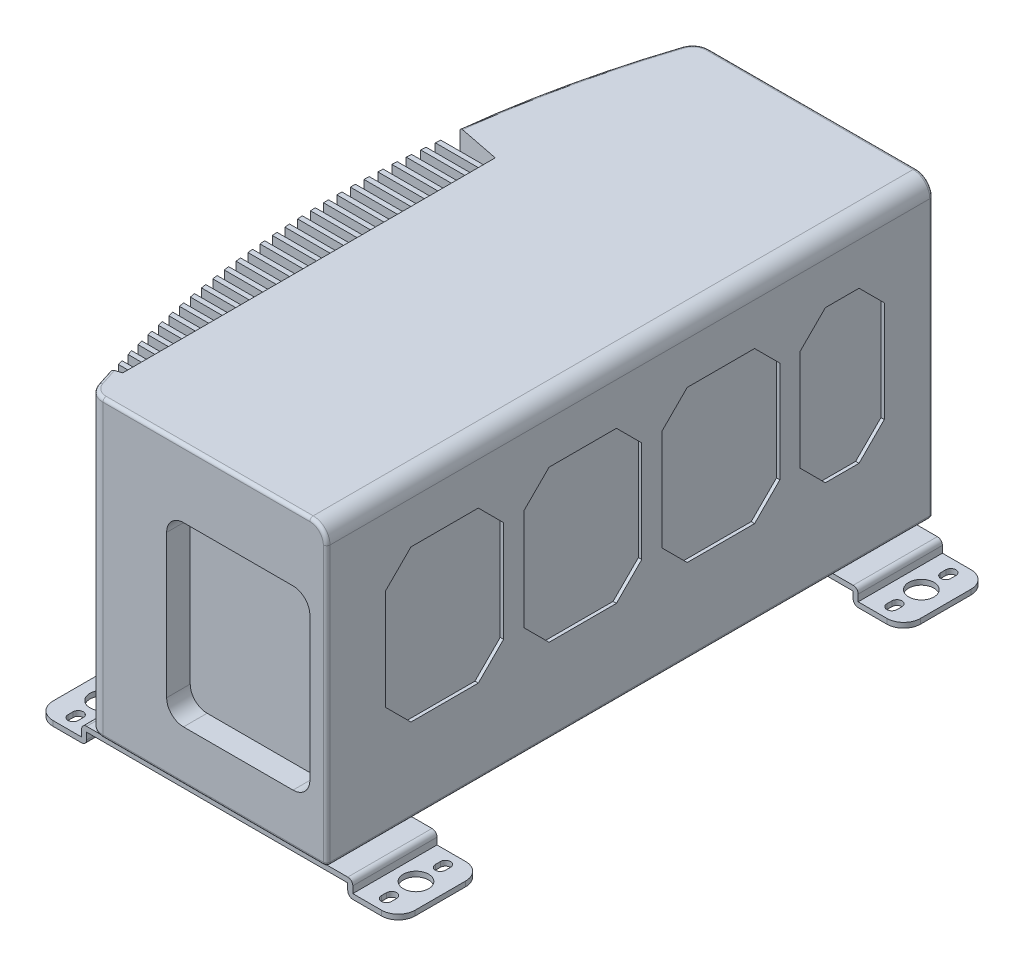
SolidWorks part; units mm, degrees
ref_plane "정면" through (0, 0, 0) normal (0, 0, 1) x (1, 0, 0)
ref_plane "윗면" through (0, 0, 0) normal (0, 1, 0) x (1, 0, 0)
ref_plane "우측면" through (0, 0, 0) normal (1, 0, 0) x (0, 0, -1)
sketch "스케치1" plane through (0, 0, 0) normal (0, 1, 0) x (1, 0, 0)
  line L0 (70, 0) -> (-100, 0) construction
  line L1 (-70, 180) -> (70, 180)
  line L2 (-70, 0) -> (-70, -180)
  line L3 (-70, -180) -> (70, -180)
  line L4 (70, 180) -> (70, -180)
  line L5 (-70, 180) -> (70, -180) construction
  line L6 (-70, -180) -> (70, 180) construction
  arc A0 (-70, 180) -> (-70, -180) centre (455, 0) ccw
  point P0 (0, 0)
  dimension "D1" = 360
  dimension "D2" = 140
  dimension "D3" = 170
extrude "보스-돌출1" add sketch "스케치1" along normal blind 175 contours L1 A0 L3 L4 region at (-10.3031, 0, 0)
sketch "스케치2" plane through (0, 175, 0) normal (0, 1, 0) x (1, 0, 0)
  line L0 (70, 0) -> (-70, 0) construction
  line L1 (-70, 60) -> (-70, -160) construction
  line L2 (70, 180) -> (70, -180) construction
  line L3 (-70, -180) -> (70, -180) construction
  line L4 (-130.1744, 60) -> (-70, 60)
  line L5 (-70, 60) -> (-70, 55)
  line L6 (-70, 55) -> (-130.1744, 55)
  line L7 (-130.1744, 55) -> (-130.1744, 52)
  line L8 (-130.1744, 52) -> (-70, 52)
  line L9 (-70, 52) -> (-70, 47)
  line L10 (-70, 47) -> (-130.1744, 47)
  line L11 (-130.1744, 47) -> (-130.1744, 44)
  line L12 (-130.1744, 44) -> (-70, 44)
  line L13 (-70, 44) -> (-70, 39)
  line L14 (-70, 39) -> (-130.1744, 39)
  line L15 (-130.1744, 39) -> (-130.1744, 36)
  line L16 (-130.1744, 36) -> (-70, 36)
  line L17 (-70, 36) -> (-70, 31)
  line L18 (-70, 31) -> (-130.1744, 31)
  line L19 (-130.1744, 31) -> (-130.1744, 28)
  line L20 (-130.1744, 28) -> (-70, 28)
  line L21 (-70, 28) -> (-70, 23)
  line L22 (-70, 23) -> (-130.1744, 23)
  line L23 (-130.1744, 23) -> (-130.1744, 20)
  line L24 (-130.1744, 20) -> (-70, 20)
  line L25 (-70, 20) -> (-70, 15)
  line L26 (-70, 15) -> (-130.1744, 15)
  line L27 (-130.1744, 15) -> (-130.1744, 12)
  line L28 (-130.1744, 12) -> (-70, 12)
  line L29 (-70, 12) -> (-70, 7)
  line L30 (-70, 7) -> (-130.1744, 7)
  line L31 (-130.1744, 7) -> (-130.1744, 4)
  line L32 (-130.1744, 4) -> (-70, 4)
  line L33 (-70, 4) -> (-70, -1)
  line L34 (-70, -1) -> (-130.1744, -1)
  line L35 (-130.1744, -1) -> (-130.1744, -4)
  line L36 (-130.1744, -4) -> (-70, -4)
  line L37 (-70, -4) -> (-70, -9)
  line L38 (-70, -9) -> (-130.1744, -9)
  line L39 (-130.1744, -9) -> (-130.1744, -12)
  line L40 (-130.1744, -12) -> (-70, -12)
  line L41 (-70, -12) -> (-70, -17)
  line L42 (-70, -17) -> (-130.1744, -17)
  line L43 (-130.1744, -17) -> (-130.1744, -20)
  line L44 (-130.1744, -20) -> (-70, -20)
  line L45 (-70, -20) -> (-70, -25)
  line L46 (-70, -25) -> (-130.1744, -25)
  line L47 (-130.1744, -25) -> (-130.1744, -28)
  line L48 (-130.1744, -28) -> (-70, -28)
  line L49 (-70, -28) -> (-70, -33)
  line L50 (-70, -33) -> (-130.1744, -33)
  line L51 (-130.1744, -33) -> (-130.1744, -36)
  line L52 (-130.1744, -36) -> (-70, -36)
  line L53 (-70, -36) -> (-70, -41)
  line L54 (-70, -41) -> (-130.1744, -41)
  line L55 (-130.1744, -41) -> (-130.1744, -44)
  line L56 (-130.1744, -44) -> (-70, -44)
  line L57 (-70, -44) -> (-70, -49)
  line L58 (-70, -49) -> (-130.1744, -49)
  line L59 (-130.1744, -49) -> (-130.1744, -52)
  line L60 (-130.1744, -52) -> (-70, -52)
  line L61 (-70, -52) -> (-70, -57)
  line L62 (-70, -57) -> (-130.1744, -57)
  line L63 (-130.1744, -57) -> (-130.1744, -60)
  line L64 (-130.1744, -60) -> (-70, -60)
  line L65 (-70, -60) -> (-70, -65)
  line L66 (-70, -65) -> (-130.1744, -65)
  line L67 (-130.1744, -65) -> (-130.1744, -68)
  line L68 (-130.1744, -68) -> (-70, -68)
  line L69 (-70, -68) -> (-70, -73)
  line L70 (-70, -73) -> (-130.1744, -73)
  line L71 (-130.1744, -73) -> (-130.1744, -76)
  line L72 (-130.1744, -76) -> (-70, -76)
  line L73 (-70, -76) -> (-70, -81)
  line L74 (-70, -81) -> (-130.1744, -81)
  line L75 (-130.1744, -81) -> (-130.1744, -84)
  line L76 (-130.1744, -84) -> (-70, -84)
  line L77 (-70, -84) -> (-70, -89)
  line L78 (-70, -89) -> (-130.1744, -89)
  line L79 (-130.1744, -89) -> (-130.1744, -92)
  line L80 (-130.1744, -92) -> (-70, -92)
  line L81 (-70, -92) -> (-70, -97)
  line L82 (-70, -97) -> (-130.1744, -97)
  line L83 (-130.1744, -97) -> (-130.1744, -100)
  line L84 (-130.1744, -100) -> (-70, -100)
  line L85 (-70, -100) -> (-70, -105)
  line L86 (-70, -105) -> (-130.1744, -105)
  line L87 (-130.1744, -105) -> (-130.1744, -108)
  line L88 (-130.1744, -108) -> (-70, -108)
  line L89 (-70, -108) -> (-70, -113)
  line L90 (-70, -113) -> (-130.1744, -113)
  line L91 (-130.1744, -113) -> (-130.1744, -116)
  line L92 (-130.1744, -116) -> (-70, -116)
  line L93 (-70, -116) -> (-70, -121)
  line L94 (-70, -121) -> (-130.1744, -121)
  line L95 (-130.1744, -121) -> (-130.1744, -124)
  line L96 (-130.1744, -124) -> (-70, -124)
  line L97 (-70, -124) -> (-70, -129)
  line L98 (-70, -129) -> (-130.1744, -129)
  line L99 (-130.1744, -129) -> (-130.1744, -132)
  line L100 (-130.1744, -132) -> (-70, -132)
  line L101 (-70, -132) -> (-70, -137)
  line L102 (-70, -137) -> (-130.1744, -137)
  line L103 (-130.1744, -137) -> (-130.1744, -140)
  line L104 (-130.1744, -140) -> (-70, -140)
  line L105 (-70, -140) -> (-70, -145)
  line L106 (-70, -145) -> (-130.1744, -145)
  line L107 (-130.1744, -145) -> (-130.1744, -148)
  line L108 (-130.1744, -148) -> (-70, -148)
  line L109 (-70, -148) -> (-70, -153)
  line L110 (-70, -153) -> (-130.1744, -153)
  line L111 (-130.1744, -153) -> (-130.1744, -156)
  line L112 (-130.1744, -156) -> (-70, -156)
  line L113 (-70, -156) -> (-70, -161)
  line L114 (-70, -161) -> (-130.1744, -161)
  line L115 (-130.1744, -161) -> (-136.4654, -161)
  line L116 (-130.1744, -161) -> (-130.1744, -164) [skipped]
  line L117 (-136.4654, -161) -> (-136.4654, 60)
  line L119 (-136.4654, 60) -> (-130.1744, 60)
  dimension "D1" = 140
  dimension "D2" = 240
  dimension "D3" = 20
  dimension "D4" = 5
  dimension "D5" = 3
  dimension "D6" = 28
extrude "컷-돌출1" cut sketch "스케치2" against normal blind 175
chamfer "모따기1" distance 27 distance2 5 1 edges at (-96.7472, 87.5, -60) first distance on face at (-83.3736, 87.5, -60)
chamfer "모따기2" distance 6.2 distance2 2 1 edges at (-76.1346, 87.5, 161) first distance on face at (-73.0673, 87.5, 161)
sketch "스케치3" plane through (0, 175, 0) normal (0, 1, 0) x (1, 0, 0)
  line L0 (-96.1544, 65.2211) -> (-70, 60.0546)
  line L1 (-70, 60.0546) -> (-70, -161.0238)
  line L2 (-70, -161.0238) -> (-75.5444, -162.9345)
  line L3 (-75.5444, -162.9345) -> (-119.8747, -162.9345)
  line L4 (-119.8747, -162.9345) -> (-119.8747, 65.2211)
  line L5 (-119.8747, 65.2211) -> (-96.1544, 65.2211)
extrude "컷-돌출2" cut sketch "스케치3" against normal blind 2
sketch "스케치4" plane through (0, 0, 180) normal (0, 0, 1) x (1, 0, 0)
  line L1 (-25, 135) -> (60, 135)
  line L2 (-25, 135) -> (-25, 30)
  line L3 (-25, 30) -> (60, 30)
  line L4 (60, 135) -> (60, 30)
  line L5 (-25, 135) -> (60, 30) construction
  line L6 (-25, 30) -> (60, 135) construction
  line L7 (-70, 0) -> (70, 0) construction
  line L8 (70, 175) -> (70, 0) construction
  point P0 (17.5, 82.5)
  dimension "D1" = 85
  dimension "D2" = 105
  dimension "D3" = 30
  dimension "D4" = 10
extrude "컷-돌출3" cut sketch "스케치4" against normal blind 14
sketch "스케치5" plane through (70, 0, 0) normal (1, 0, 0) x (0, 0, -1)
  line L0 (-180, 175) -> (-180, 0) construction
  line L1 (-130, 140) -> (-90, 140)
  line L2 (-145, 125) -> (-145, 65)
  line L3 (-130, 50) -> (-90, 50)
  line L4 (-75, 125) -> (-75, 65)
  line L5 (-145, 140) -> (-75, 50) construction
  line L6 (-145, 50) -> (-75, 140) construction
  line L7 (-8, 140) -> (-48, 140)
  line L8 (7, 125) -> (7, 65)
  line L9 (-8, 50) -> (-48, 50)
  line L10 (-63, 125) -> (-63, 65)
  line L11 (7, 140) -> (-63, 50) construction
  line L12 (7, 50) -> (-63, 140) construction
  line L13 (74, 140) -> (34, 140)
  line L14 (89, 125) -> (89, 65)
  line L15 (74, 50) -> (34, 50)
  line L16 (19, 125) -> (19, 65)
  line L17 (89, 140) -> (19, 50) construction
  line L18 (89, 50) -> (19, 140) construction
  line L19 (136, 140) -> (116, 140)
  line L20 (151, 125) -> (151, 65)
  line L21 (136, 50) -> (116, 50)
  line L22 (101, 125) -> (101, 65)
  line L23 (151, 140) -> (101, 50) construction
  line L24 (151, 50) -> (101, 140) construction
  line L25 (180, 175) -> (-180, 175) construction
  line L26 (-145, 125) -> (-130, 140)
  line L27 (-90, 140) -> (-75, 125)
  line L28 (-145, 65) -> (-130, 50)
  line L29 (-90, 50) -> (-75, 65)
  line L30 (-48, 140) -> (-63, 125)
  line L31 (7, 125) -> (-8, 140)
  line L32 (-48, 50) -> (-63, 65)
  line L33 (7, 65) -> (-8, 50)
  line L34 (34, 140) -> (19, 125)
  line L35 (89, 125) -> (74, 140)
  line L36 (34, 50) -> (19, 65)
  line L37 (89, 65) -> (74, 50)
  line L38 (116, 140) -> (101, 125)
  line L39 (116, 50) -> (101, 65)
  line L40 (151, 65) -> (136, 50)
  line L41 (151, 125) -> (136, 140)
  point P0 (-110, 95)
  point P5 (-28, 95)
  point P10 (54, 95)
  point P15 (126, 95)
  point P20 (150.3107, 100.7289)
  point P21 (126.9205, 56.2492)
  point P22 (125.3867, 145.2086)
  dimension "D1" = 35
  dimension "D2" = 12
  dimension "D3" = 12
  dimension "D4" = 12
  dimension "D5" = 35
  dimension "D6" = 90
  dimension "D7" = 70
  dimension "D8" = 70
  dimension "D9" = 70
  dimension "D10" = 50
extrude "컷-돌출4" cut sketch "스케치5" against normal blind 2
sketch "스케치6" plane through (0, 0, -180) normal (0, 0, -1) x (-1, 0, 0)
  line L1 (33, 45) -> (-38, 45)
  line L2 (55, 67) -> (55, 138)
  line L3 (33, 160) -> (-38, 160)
  line L4 (-60, 67) -> (-60, 138)
  line L5 (55, 45) -> (-60, 160) construction
  line L6 (55, 160) -> (-60, 45) construction
  line L8 (-38, 160) -> (-45.2888, 152.7112)
  line L9 (-38, 45) -> (-45.4645, 52.4645)
  line L10 (55, 67) -> (47.7112, 59.7112)
  line L11 (55, 138) -> (47.5355, 145.4645)
  line L12 (40.4645, 152.5355) -> (14.881, 126.952)
  line L13 (-45.2888, 152.7112) -> (-19.6749, 127.0972)
  line L14 (47.7112, 59.7112) -> (22.0972, 85.3251)
  line L15 (47.5355, 145.4645) -> (21.952, 119.881)
  line L16 (40.2888, 52.2888) -> (14.6749, 77.9028)
  line L17 (-45.4645, 52.4645) -> (-19.881, 78.048)
  line L18 (-52.5355, 59.5355) -> (-26.952, 85.119)
  line L19 (-52.7112, 145.2888) -> (-27.0972, 119.6749)
  line L20 (-52.7112, 145.2888) -> (-60, 138)
  line L21 (-52.5355, 59.5355) -> (-60, 67)
  line L22 (40.2888, 52.2888) -> (33, 45)
  line L23 (40.4645, 152.5355) -> (33, 160)
  arc A0 (14.881, 126.952) -> (-19.6749, 127.0972) centre (-2.5, 102.5) ccw
  arc A1 (22.0972, 85.3251) -> (21.952, 119.881) centre (-2.5, 102.5) ccw
  arc A2 (-19.881, 78.048) -> (14.6749, 77.9028) centre (-2.5, 102.5) ccw
  arc A3 (-27.0972, 119.6749) -> (-26.952, 85.119) centre (-2.5, 102.5) ccw
  point P0 (-2.5, 102.5)
  point P19 (-175.0817, 87.3794)
  point P23 (0, 0)
  dimension "D5" = 60
  dimension "D3" = 115
  dimension "D4" = 115
  dimension "D6" = 5
  dimension "D10" = 22
extrude "컷-돌출5" cut sketch "스케치6" against normal blind 2
fillet "필렛1" radius 10 7 edges at (-70, 87.5, 180) (-70, 87.5, -180) (70, 175, 0) (-25, 30, 173) (60, 30, 173) (60, 135, 173) (-25, 135, 173)
fillet "필렛2" radius 2 17 edges at (-73.9512, 0, 168.0347) (-68.6733, 0, 178.0992) (3.5961, 0, -180) (-68.6733, 0, -178.0992) (70, 82.5, 180) (67.0711, 172.0711, 180) (-1.4039, 175, 180) (-68.6733, 175, 178.0992) (70, 82.5, -180) (67.0711, 172.0711, -180) (-1.4039, 175, -180) (-68.6733, 175, -178.0992) (3.5961, 0, 180) (70, 0, 0) (-86.9237, 0, -119.7651) (-73.9512, 175, 168.0347) (-86.9237, 175, -119.7651)
sketch "스케치7" plane through (0, 0, 0) normal (0, 0, 1) x (1, 0, 0)
  line L0 (80.5, -3.4607) -> (-80.5, -3.4607)
  line L1 (-80.5, -3.4607) -> (-80.5, -10.4607)
  line L2 (-80.5, -10.4607) -> (-107.5, -10.4607)
  line L3 (-107.5, -10.4607) -> (-107.5, -13.4607)
  line L4 (-107.5, -13.4607) -> (-77.5, -13.4607)
  line L5 (-77.5, -13.4607) -> (-77.5, -6.4607)
  line L6 (-77.5, -6.4607) -> (77.5, -6.4607)
  line L7 (77.5, -6.4607) -> (77.5, -13.4607)
  line L8 (77.5, -13.4607) -> (107.5, -13.4607)
  line L9 (107.5, -13.4607) -> (107.5, -10.4607)
  line L10 (107.5, -10.4607) -> (80.5, -10.4607)
  line L11 (80.5, -10.4607) -> (80.5, -3.4607)
  point P10 (0, -6.4607)
  dimension "D1" = 3
  dimension "D2" = 3
  dimension "D3" = 3
  dimension "D4" = 3
  dimension "D5" = 3
  dimension "D6" = 155
  dimension "D7" = 30
  dimension "D8" = 30
  dimension "D9" = 10
  dimension "D10" = 10
extrude "보스-돌출2" add sketch "스케치7" along normal mid plane 350 separate body
sketch "스케치9" plane through (0, 0, 0) normal (0, 0, 1) x (1, 0, 0)
  line L12 (80.5, -10.4607) -> (80.5, -3.4607)
  line L13 (80.5, -3.4607) -> (-80.5, -3.4607)
  line L14 (-80.5, -3.4607) -> (-80.5, -10.4607)
  line L15 (-80.5, -10.4607) -> (-107.5, -10.4607)
  line L16 (-107.5, -10.4607) -> (-107.5, -13.4607)
  line L17 (-107.5, -13.4607) -> (-77.5, -13.4607)
  line L18 (-77.5, -13.4607) -> (-77.5, -6.4607)
  line L19 (-77.5, -6.4607) -> (77.5, -6.4607)
  line L20 (77.5, -6.4607) -> (77.5, -13.4607)
  line L21 (77.5, -13.4607) -> (107.5, -13.4607)
  line L22 (107.5, -13.4607) -> (107.5, -10.4607)
  line L23 (107.5, -10.4607) -> (80.5, -10.4607)
  line L24 (80.5, -10.4607) -> (80.5, -3.4607)
  line L25 (80.5, -3.4607) -> (-80.5, -3.4607)
  line L26 (-80.5, -3.4607) -> (-80.5, -10.4607)
  line L27 (-80.5, -10.4607) -> (-107.5, -10.4607)
  line L28 (-107.5, -10.4607) -> (-107.5, -13.4607)
  line L29 (-107.5, -13.4607) -> (-77.5, -13.4607)
  line L30 (-77.5, -13.4607) -> (-77.5, -6.4607)
  line L31 (-77.5, -6.4607) -> (77.5, -6.4607)
  line L32 (77.5, -6.4607) -> (77.5, -13.4607)
  line L33 (77.5, -13.4607) -> (107.5, -13.4607)
  line L34 (107.5, -13.4607) -> (107.5, -10.4607)
  line L35 (107.5, -10.4607) -> (80.5, -10.4607)
  dimension "D1" = 0
extrude "컷-돌출6" cut sketch "스케치9" against normal mid plane 250
fillet "필렛3" radius 3 4 edges at (-77.5, -13.4607, 150) (-80.5, -3.4607, 150) (77.5, -13.4607, 150) (80.5, -3.4607, 150)
fillet "필렛4" radius 3 4 edges at (-77.5, -13.4607, -150) (-80.5, -3.4607, -150) (77.5, -13.4607, -150) (80.5, -3.4607, -150)
fillet "필렛5" radius 10 4 edges at (-107.5, -11.9607, 125) (-107.5, -11.9607, 175) (107.5, -11.9607, 125) (107.5, -11.9607, 175)
fillet "필렛6" radius 10 4 edges at (107.5, -11.9607, -125) (107.5, -11.9607, -175) (-107.5, -11.9607, -175) (-107.5, -11.9607, -125)
sketch "스케치10" plane through (0, -3.4607, 0) normal (0, 1, 0) x (1, 0, 0)
  line L0 (107.5, 135) -> (107.5, 165) construction
  line L1 (-107.5, 135) -> (-107.5, 165) construction
  line L2 (0, 0) -> (35.4855, 0) construction
  circle A0 centre (-42.5, 150) radius 10
  circle A1 centre (42.5, 150) radius 10
  circle A2 centre (42.5, -150) radius 10
  circle A3 centre (-42.5, -150) radius 10
  point P6 (107.5, 150)
  dimension "D1" = 20
  dimension "D2" = 65
  dimension "D3" = 65
extrude "보스-돌출3" add sketch "스케치10" along normal up to next
sketch "스케치11" plane through (0, -13.4607, 0) normal (0, -1, 0) x (1, 0, 0)
  line L0 (107.5, 165) -> (107.5, 135) construction
  line L1 (93, 150) -> (107.5, 150) construction
  line L2 (93, 125) -> (93, 175) construction
  line L3 (80.5, 125) -> (97.5, 125) construction
  line L4 (80.5, 175) -> (97.5, 175) construction
  line L5 (93, 167.5) -> (93, 164.5) construction
  line L6 (96, 167.5) -> (96, 164.5)
  line L7 (90, 167.5) -> (90, 164.5)
  line L8 (93, 132.5) -> (93, 135.5) construction
  line L9 (96, 132.5) -> (96, 135.5)
  line L10 (90, 132.5) -> (90, 135.5)
  line L11 (0, 0) -> (28.6518, 0) construction
  line L12 (0, 0) -> (0, 45.201) construction
  line L13 (-93, 167.5) -> (-93, 164.5) construction
  line L14 (-96, 167.5) -> (-96, 164.5)
  line L15 (-90, 167.5) -> (-90, 164.5)
  line L16 (-93, 132.5) -> (-93, 135.5) construction
  line L17 (-96, 132.5) -> (-96, 135.5)
  line L18 (-90, 132.5) -> (-90, 135.5)
  line L19 (-93, 125) -> (-93, 175) construction
  line L20 (-93, 150) -> (-107.5, 150) construction
  line L21 (-93, -167.5) -> (-93, -164.5) construction
  line L22 (-96, -167.5) -> (-96, -164.5)
  line L23 (-90, -167.5) -> (-90, -164.5)
  line L24 (-93, -132.5) -> (-93, -135.5) construction
  line L25 (-96, -132.5) -> (-96, -135.5)
  line L26 (-90, -132.5) -> (-90, -135.5)
  line L27 (93, -167.5) -> (93, -164.5) construction
  line L28 (96, -167.5) -> (96, -164.5)
  line L29 (90, -167.5) -> (90, -164.5)
  line L30 (93, -132.5) -> (93, -135.5) construction
  line L31 (96, -132.5) -> (96, -135.5)
  line L32 (90, -132.5) -> (90, -135.5)
  line L33 (93, -125) -> (93, -175) construction
  line L34 (93, -150) -> (107.5, -150) construction
  line L35 (-93, -150) -> (-107.5, -150) construction
  line L36 (-93, -125) -> (-93, -175) construction
  circle A0 centre (93, 150) radius 7.5
  arc A1 (96, 167.5) -> (90, 167.5) centre (93, 167.5) ccw
  arc A2 (90, 164.5) -> (96, 164.5) centre (93, 164.5) ccw
  arc A3 (96, 132.5) -> (90, 132.5) centre (93, 132.5) cw
  arc A4 (90, 135.5) -> (96, 135.5) centre (93, 135.5) cw
  arc A5 (-96, 167.5) -> (-90, 167.5) centre (-93, 167.5) cw
  arc A6 (-90, 164.5) -> (-96, 164.5) centre (-93, 164.5) cw
  arc A7 (-96, 132.5) -> (-90, 132.5) centre (-93, 132.5) ccw
  arc A8 (-90, 135.5) -> (-96, 135.5) centre (-93, 135.5) ccw
  circle A9 centre (-93, 150) radius 7.5
  arc A10 (-96, -167.5) -> (-90, -167.5) centre (-93, -167.5) ccw
  arc A11 (-90, -164.5) -> (-96, -164.5) centre (-93, -164.5) ccw
  arc A12 (-96, -132.5) -> (-90, -132.5) centre (-93, -132.5) cw
  arc A13 (-90, -135.5) -> (-96, -135.5) centre (-93, -135.5) cw
  arc A14 (96, -167.5) -> (90, -167.5) centre (93, -167.5) cw
  arc A15 (90, -164.5) -> (96, -164.5) centre (93, -164.5) cw
  arc A16 (96, -132.5) -> (90, -132.5) centre (93, -132.5) ccw
  arc A17 (90, -135.5) -> (96, -135.5) centre (93, -135.5) ccw
  circle A18 centre (93, -150) radius 7.5
  circle A19 centre (-93, -150) radius 7.5
  point P4 (107.5, 150)
  point P14 (93, 166)
  point P21 (93, 134)
  point P32 (-93, 166)
  point P39 (-93, 134)
  point P51 (-93, -166)
  point P58 (-93, -134)
  point P65 (93, -166)
  point P72 (93, -134)
  dimension "D1" = 15
  dimension "D5" = 3
  dimension "D2" = 14.5
  dimension "D3" = 16
  dimension "D4" = 3
extrude "컷-돌출7" cut sketch "스케치11" against normal up to next
